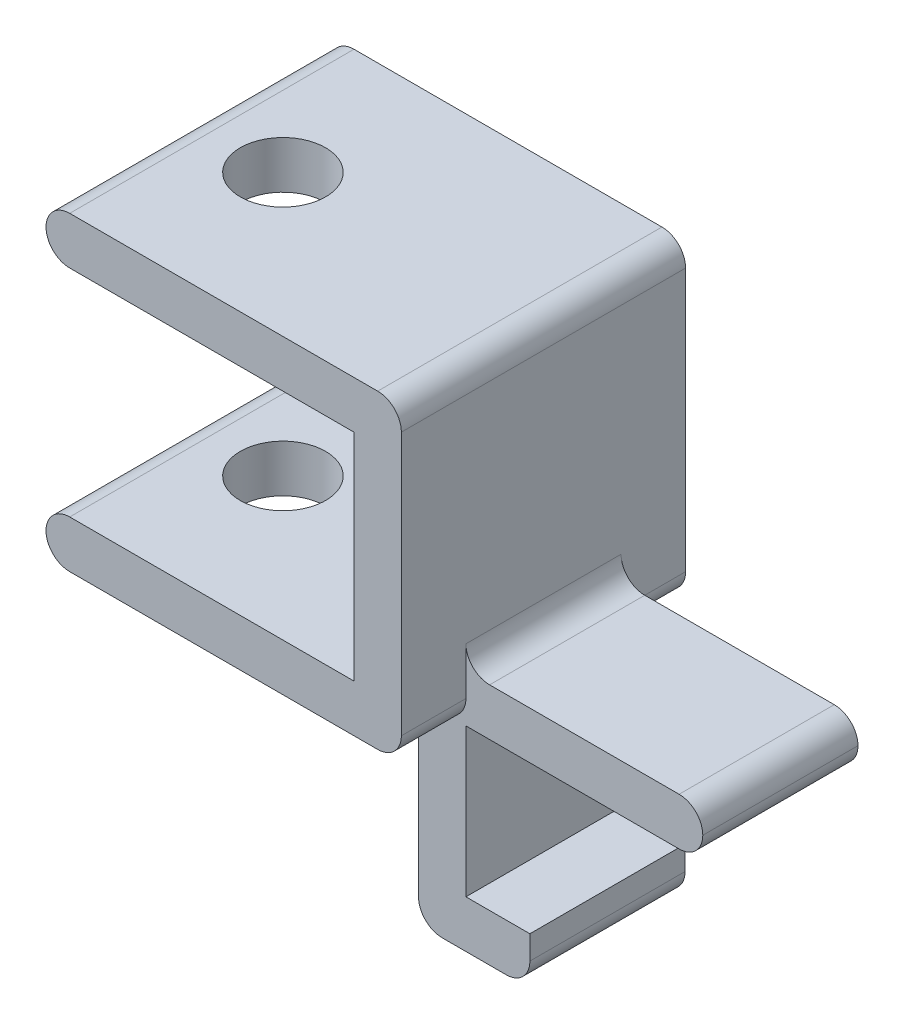
SolidWorks part; units mm, degrees
ref_plane "Front Plane" through (0, 0, 0) normal (0, 0, 1) x (1, 0, 0)
ref_plane "Top Plane" through (0, 0, 0) normal (0, 1, 0) x (1, 0, 0)
ref_plane "Right Plane" through (0, 0, 0) normal (1, 0, 0) x (0, 0, -1)
sketch "Sketch1" plane through (0, 0, 0) normal (0, 0, 1) x (1, 0, 0)
  line L1 (0, 0) -> (-13, 0)
  line L2 (0, 0) -> (0, -9.1)
  line L3 (0, -9.1) -> (-13, -9.1)
  line L4 (-13, 2) -> (-13, 0)
  line L5 (2, -11.1) -> (-13, -11.1)
  line L6 (2, 2) -> (2, -11.1)
  line L7 (2, 2) -> (-13, 2)
  line L8 (0, 0) -> (-13, 0) construction
  line L9 (-13, 0) -> (-13, -9.1) construction
  line L10 (2, 2) -> (-15, 2) construction
  line L11 (-15, 2) -> (-15, -11.1) construction
  line L12 (-13, -9.1) -> (-13, -11.1)
  line L13 (2, -11.1) -> (-15, -11.1) construction
  line L14 (2, -11.1) -> (2, -17.35)
  line L15 (2, -17.35) -> (4.7, -17.35)
  line L16 (0, -11.1) -> (0, -19.35)
  line L17 (0, -19.35) -> (4.7, -19.35)
  line L18 (4.7, -17.35) -> (4.7, -19.35)
  line L19 (2, -11.1) -> (12, -11.1)
  line L20 (12, -11.1) -> (12, -9.1)
  line L21 (12, -9.1) -> (2, -9.1)
  dimension "D1" = 9.1
  dimension "D2" = 13
  dimension "D4" = 2
  dimension "D7" = 10
  dimension "D5" = 2.7
  dimension "D6" = 6.25
  dimension "D3" = 2
extrude "Boss-Extrude1" add sketch "Sketch1" along normal mid plane 6.55
extrude "Boss-Extrude2" add sketch "Sketch1<3>" along normal mid plane 12 contours L3 L12 L5 L6 L7 L4 L1 L2 region at (-6.5, 0.1992, 0)
sketch "Sketch1<3>" plane through (0, 0, 0) normal (0, 0, 1) x (1, 0, 0) same geometry as "Sketch1"
fillet "Fillet1" radius 1 13 edges at (-13, -11.1, 0) (-13, -9.1, 0) (-13, 0, 0) (-13, 2, 0) (2, 2, 0) (12, -11.1, 0) (0, -19.35, 0) (4.7, -19.35, 0) (2, -9.1, 0) (12, -9.1, 0) (0, -11.1, 0) (2, -11.1, -4.6375) (2, -11.1, 4.6375)
sketch "Sketch2" plane through (0, 2, 0) normal (0, 1, 0) x (1, 0, 0)
  line L0 (-12, 6) -> (-12, -6) construction
  circle A0 centre (-9, 0) radius 1.8
  point P2 (0, 0)
  point P6 (-12, 0)
  dimension "D2" = 3.6
  dimension "D1" = 9
extrude "Cut-Extrude1" cut sketch "Sketch2" against normal through all both and the other way through all
